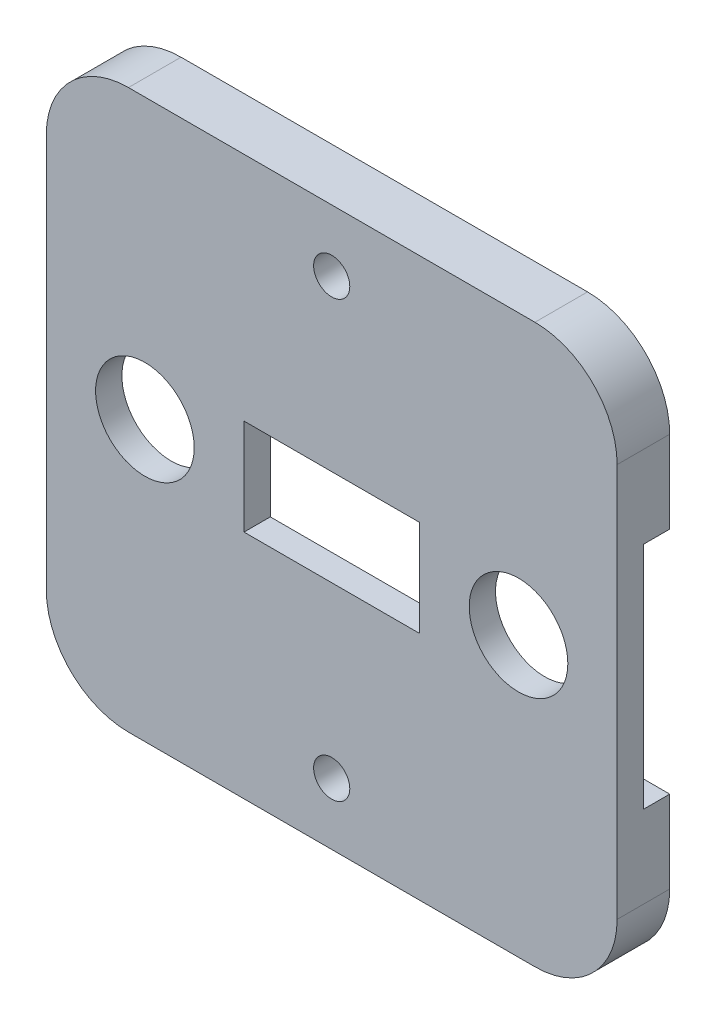
SolidWorks part; units mm, degrees
ref_plane "Front Plane" through (0, 0, 0) normal (0, 0, 1) x (1, 0, 0)
ref_plane "Top Plane" through (0, 0, 0) normal (0, 1, 0) x (1, 0, 0)
ref_plane "Right Plane" through (0, 0, 0) normal (1, 0, 0) x (0, 0, -1)
sketch "Sketch1" plane through (0, 0, 0) normal (0, 0, 1) x (1, 0, 0)
  line L1 (-22.0535, -18.6229) -> (-22.0535, -12.2729)
  line L2 (-15.7035, -5.9229) -> (15.7036, -5.9229)
  line L51 (-9.4424, -18.6229) -> (21.5953, -18.6229)
  line L52 (-22.0535, -18.6229) -> (22.0536, -18.6229) construction
  line L54 (-9.4424, -36.3521) -> (21.5953, -36.3521)
  line L55 (-22.0535, -36.3521) -> (22.0536, -36.3521) construction
  line L56 (-22.0535, -36.3521) -> (22.0536, -36.3521)
  line L57 (-22.0535, -36.3521) -> (-22.0535, -42.7021)
  line L58 (-15.7035, -49.0521) -> (15.7036, -49.0521)
  line L59 (22.0536, -36.3521) -> (22.0536, -42.7021)
  line L60 (22.0536, -18.6229) -> (-22.0535, -18.6229)
  line L61 (22.0536, -18.6229) -> (22.0536, -12.2729)
  circle A0 centre (-14.4335, -27.4875) radius 1.319 construction
  circle A1 centre (14.4336, -27.4875) radius 1.319 construction
  circle A2 centre (-14.4335, -27.4875) radius 1.319 construction
  circle A3 centre (14.4336, -27.4875) radius 1.319 construction
  arc A8 (-15.7035, -49.0521) -> (-22.0535, -42.7021) centre (-15.7035, -42.7021) cw
  arc A9 (15.7036, -49.0521) -> (22.0536, -42.7021) centre (15.7036, -42.7021) ccw
  arc A10 (15.7036, -5.9229) -> (22.0536, -12.2729) centre (15.7036, -12.2729) cw
  arc A11 (-22.0535, -12.2729) -> (-15.7035, -5.9229) centre (-15.7035, -12.2729) cw
  point P3 (-22.0535, -49.0521)
  point P21 (-22.0535, -49.0521)
  dimension "D6" = 7.62
  dimension "D4" = 6.35
  dimension "D3" = 12.7
  dimension "D5" = 7.62
  dimension "D1" = 0.508
  dimension "D2" = 0.508
extrude "Boss-Extrude1" add sketch "Sketch1" along normal offset from surface (4.064 mm away) 2.54 contours L60 L1 A11 L2 A10 L61 | L58 A9 L59 L56 L57 A8 offset beyond the face yes
sketch "Sketch2" plane through (0, 0, 4.064) normal (0, 0, 1) x (1, 0, 0)
  line L0 (-6.0134, -30.2624) -> (-6.0134, -30.4402) construction
  line L1 (-22.0535, -39.5271) -> (22.0536, -39.5271)
  line L7 (22.0536, -15.4479) -> (-22.0535, -15.4479)
  line L9 (-6.0134, -30.2624) -> (-6.0134, -24.7125) construction
  line L10 (-6.0134, -24.5347) -> (-6.0134, -24.7125) construction
  line L11 (6.0135, -24.5347) -> (-6.0134, -24.5347) construction
  line L12 (6.0135, -30.4402) -> (6.0135, -24.5347) construction
  line L13 (-6.0134, -30.4402) -> (6.0135, -30.4402) construction
  line L14 (-6.0134, -30.2624) -> (-6.0134, -30.4402) construction
  line L15 (-6.0134, -30.2624) -> (-6.0134, -24.7125) construction
  line L16 (-6.0134, -24.5347) -> (-6.0134, -24.7125) construction
  line L17 (6.0135, -24.5347) -> (-6.0134, -24.5347) construction
  line L18 (6.0135, -30.4402) -> (6.0135, -24.5347) construction
  line L19 (-6.0134, -30.4402) -> (6.0135, -30.4402) construction
  line L20 (-6.7754, -23.7727) -> (-6.7754, -24.7125)
  line L21 (-6.7754, -30.2624) -> (-6.7754, -24.7125)
  line L26 (-6.7754, -30.2624) -> (-6.7754, -31.2022)
  line L27 (-6.7754, -31.2022) -> (6.7755, -31.2022)
  line L30 (6.7755, -31.2022) -> (6.7755, -23.7727)
  line L31 (6.7755, -23.7727) -> (-6.7754, -23.7727)
  line L32 (22.0536, -18.6229) -> (-22.0535, -18.6229) construction
  line L33 (-22.0535, -15.4479) -> (-22.0535, -39.5271)
  line L35 (22.0536, -39.5271) -> (22.0536, -15.4479)
  circle A0 centre (-14.4335, -27.4875) radius 1.397 construction
  circle A1 centre (14.4336, -27.4875) radius 1.397 construction
  circle A2 centre (-14.4335, -27.4875) radius 1.397 construction
  circle A3 centre (14.4336, -27.4875) radius 1.397 construction
  circle A4 centre (14.4336, -27.4875) radius 3.81
  circle A5 centre (-14.4335, -27.4875) radius 3.81
  arc A10 (9.4933, -23.6775) -> (9.4933, -31.2975) centre (9.4933, -27.4875) ccw construction
  point P37 (-6.0134, -27.4875)
  point P45 (-22.0535, -27.4875)
  dimension "D3" = 0.762
  dimension "D5" = 7.62
  dimension "D1" = 7.62
  dimension "D4" = 3.175
extrude "Boss-Extrude2" add sketch "Sketch2" against normal offset from surface (2.032 mm away) 0.508
sketch "Sketch3" plane through (0, 0, 4.064) normal (0, 0, 1) x (1, 0, 0)
  line L0 (0, -49.0521) -> (0, -44.2896) construction
  line L1 (0, -10.6854) -> (0, -5.9229) construction
  line L2 (-15.7035, -49.0521) -> (15.7036, -49.0521) construction
  line L3 (-15.7035, -5.9229) -> (15.7036, -5.9229) construction
  line L6 (-15.7035, -49.0521) -> (15.7036, -49.0521) construction
  line L7 (-15.7035, -5.9229) -> (15.7036, -5.9229) construction
  point P8 (0, 0)
  point P9 (0, 0)
  point P10 (0, 0)
  point P12 (0, -44.2896)
  point P13 (0, -10.6854)
  point P14 (0, -10.6854)
  dimension "D1" = 4.7625
hole_wizard "#3 Clearance Hole1" positions "Sketch6" profile "Sketch7" hole size "#3" standard "ANSI Inch" end condition through all
sketch "Sketch6" plane through (0, 0, 4.064) normal (0, 0, 1) x (1, 0, 0)
  point P0 (0, -10.6854)
  point P3 (0, -44.2896)
sketch "Sketch7" plane through (0, -10.6854, 4.064) normal (1, 0, 0) x (0, -1, 0)
  line L0 (0, 0) -> (0, 4.064)
  line L1 (0, 4.064) -> (1.397, 4.064)
  line L2 (1.397, 4.064) -> (1.397, 0)
  line L5 (1.397, 0) -> (0, 0)
  line L11 (0, -6.35) -> (0, 107.95) construction
  dimension "Thru Hole Dia." = 2.794
  dimension "Thru Hole Depth" = 4.064
